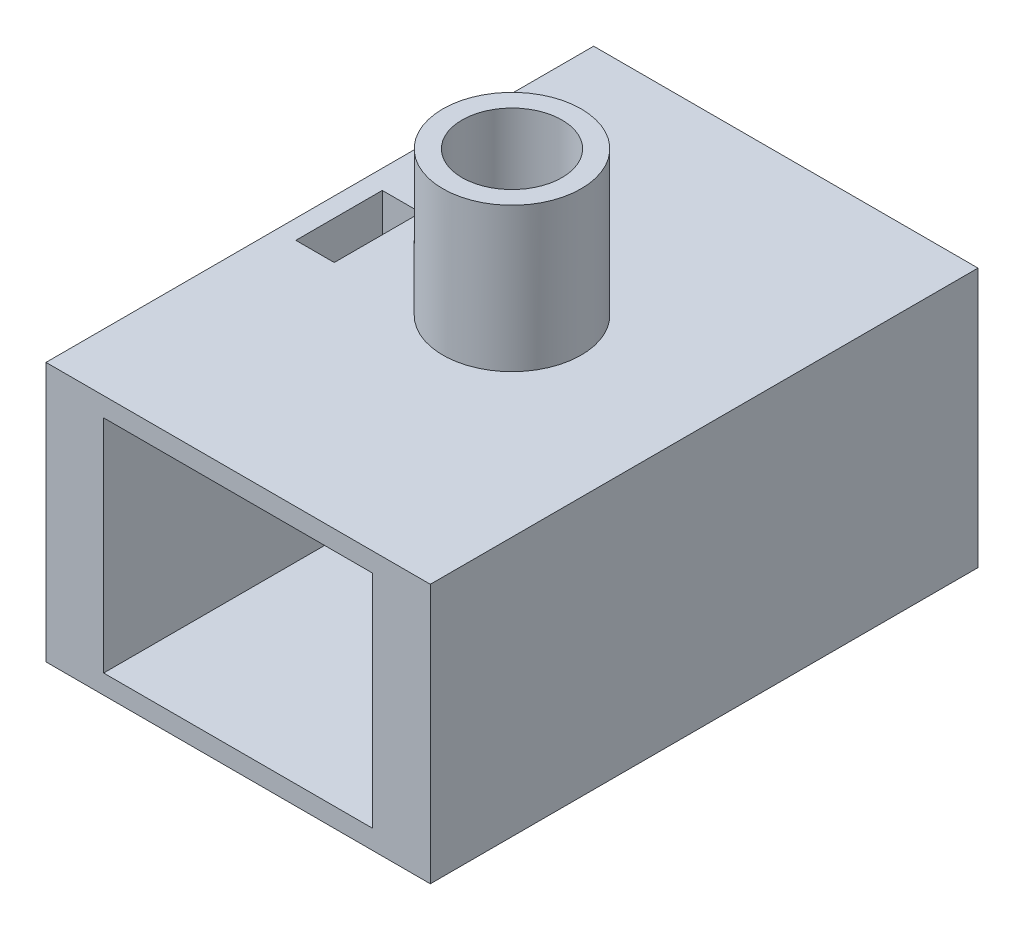
SolidWorks part; units mm, degrees
ref_plane "Plan de face" through (0, 0, 0) normal (0, 0, 1) x (1, 0, 0)
ref_plane "Plan de dessus" through (0, 0, 0) normal (0, 1, 0) x (1, 0, 0)
ref_plane "Plan de droite" through (0, 0, 0) normal (1, 0, 0) x (0, 0, -1)
sketch "Esquisse1" plane through (0, 0, 0) normal (0, 1, 0) x (1, 0, 0)
  line L1 (-20, -28.5) -> (20, -28.5)
  line L2 (-20, -28.5) -> (-20, 28.5)
  line L3 (-20, 28.5) -> (20, 28.5)
  line L4 (20, -28.5) -> (20, 28.5)
  line L5 (-20, -28.5) -> (20, 28.5) construction
  line L6 (-20, 28.5) -> (20, -28.5) construction
  point P0 (0, 0)
  dimension "D1" = 40
  dimension "D2" = 57
extrude "Boss.-Extru.1" add sketch "Esquisse1" along normal mid plane 27
sketch "Esquisse5" plane through (0, 0, 28.5) normal (0, 0, 1) x (1, 0, 0)
  line L1 (-14, -11.5) -> (14, -11.5)
  line L2 (-14, -11.5) -> (-14, 11.5)
  line L3 (-14, 11.5) -> (14, 11.5)
  line L4 (14, -11.5) -> (14, 11.5)
  line L5 (-14, -11.5) -> (14, 11.5) construction
  line L6 (-14, 11.5) -> (14, -11.5) construction
  point P0 (0, 0)
  dimension "D1" = 23
  dimension "D2" = 28
extrude "Enlèv. mat.-Extru.1" cut sketch "Esquisse5" against normal blind 55
sketch "Esquisse6" plane through (0, 13.5, 0) normal (0, 1, 0) x (1, 0, 0)
  circle A0 centre (0, 0) radius 5.2
  circle A1 centre (0, 0) radius 7.2
  circle A2 centre (0, 0) radius 4
  dimension "D1" = 10.4
  dimension "D2" = 14.4
  dimension "D3" = 8
extrude "Enlèv. mat.-Extru.2" cut sketch "Esquisse6" against normal up to next contours A2 region at (0, 13.5, 0)
extrude "Boss.-Extru.2" add sketch "Esquisse6<3>" along normal blind 15 contours A1 A0 region at (-6.9964, 13.5, 0)
sketch "Esquisse6<3>" plane through (0, 13.5, 0) normal (0, 1, 0) x (1, 0, 0) same geometry as "Esquisse6"
sketch "Esquisse7" plane through (0, 13.5, 0) normal (0, 1, 0) x (1, 0, 0)
  line L0 (-20, 28.5) -> (-20, -28.5) construction
  line L1 (-18, 4.5) -> (-14, 4.5)
  line L2 (-18, 4.5) -> (-18, -4.5)
  line L3 (-18, -4.5) -> (-14, -4.5)
  line L4 (-14, 4.5) -> (-14, -4.5)
  line L6 (-22, 0) -> (22, 0) construction
  point P4 (-18, 0)
  dimension "D1" = 9
  dimension "D2" = 4
  dimension "D3" = 2
extrude "Enlèv. mat.-Extru.3" cut sketch "Esquisse7" against normal blind 20
